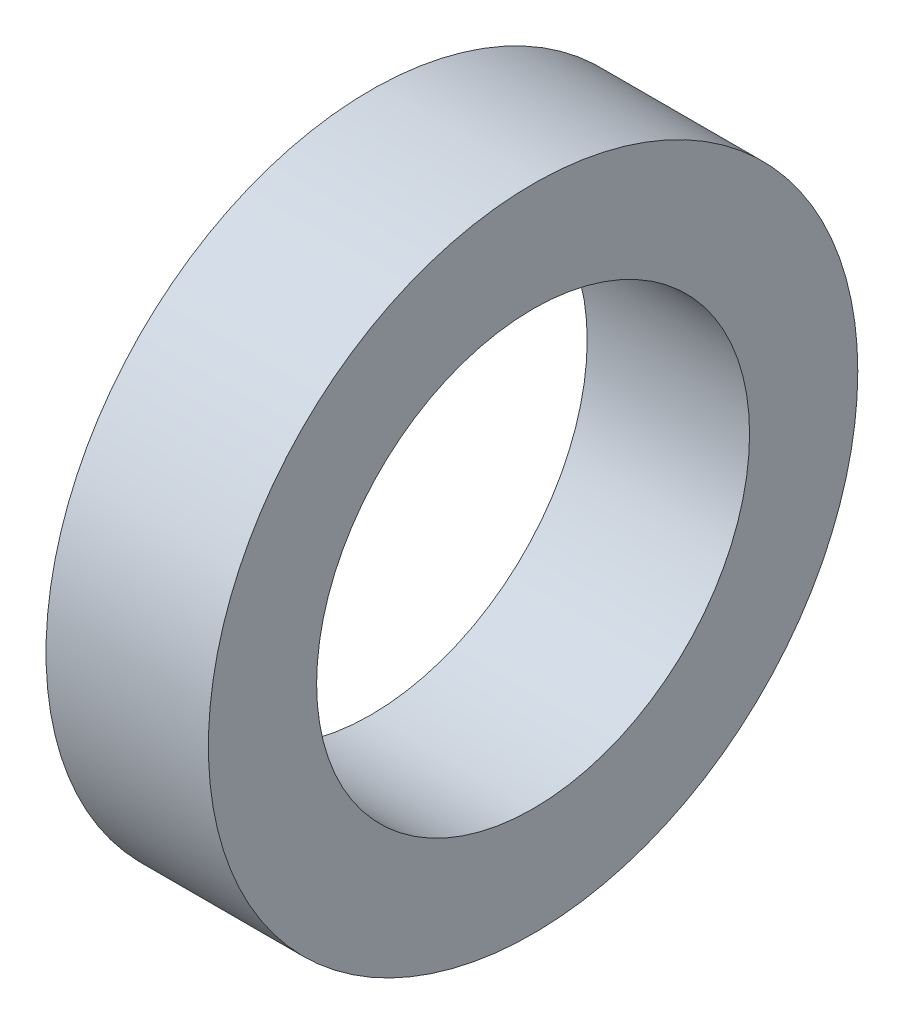
SolidWorks part; units mm, degrees
material "6061 Alloy"
ref_plane "Front Plane" through (0, 0, 0) normal (0, 0, 1) x (1, 0, 0)
ref_plane "Top Plane" through (0, 0, 0) normal (0, 1, 0) x (1, 0, 0)
ref_plane "Right Plane" through (0, 0, 0) normal (1, 0, 0) x (0, 0, -1)
sketch "Sketch2" plane through (0, 0, 0) normal (1, 0, 0) x (0, 0, -1)
  circle A0 centre (0, 0) radius 20
  circle A3 centre (0, 0) radius 30
  dimension "D1" = 40
extrude "Boss-Extrude6" add sketch "Sketch2" along normal blind 15
sketch3d "3DSketch1"
  line L0 (15, -29.9839, -0.9834) -> (0, -29.9839, -0.9834) construction
  circle A0 centre (15, 0, 0) radius 30 construction
  circle A1 centre (0, 0, 0) radius 30 construction
  point P4 (45, 0, 0)
  point P7 (30, 0, 0)
ref_axis "Axis1" through (15, 0, 0) along (-1, 0, 0)
sketch "Sketch3" plane through (15, 0, 0) normal (1, 0, 0) x (0, 0, -1)
  line L0 (20, 0) -> (30, 0) construction
  circle A0 centre (0, 0) radius 20 construction
  circle A1 centre (0, 0) radius 30 construction
  point P7 (0, 0)
